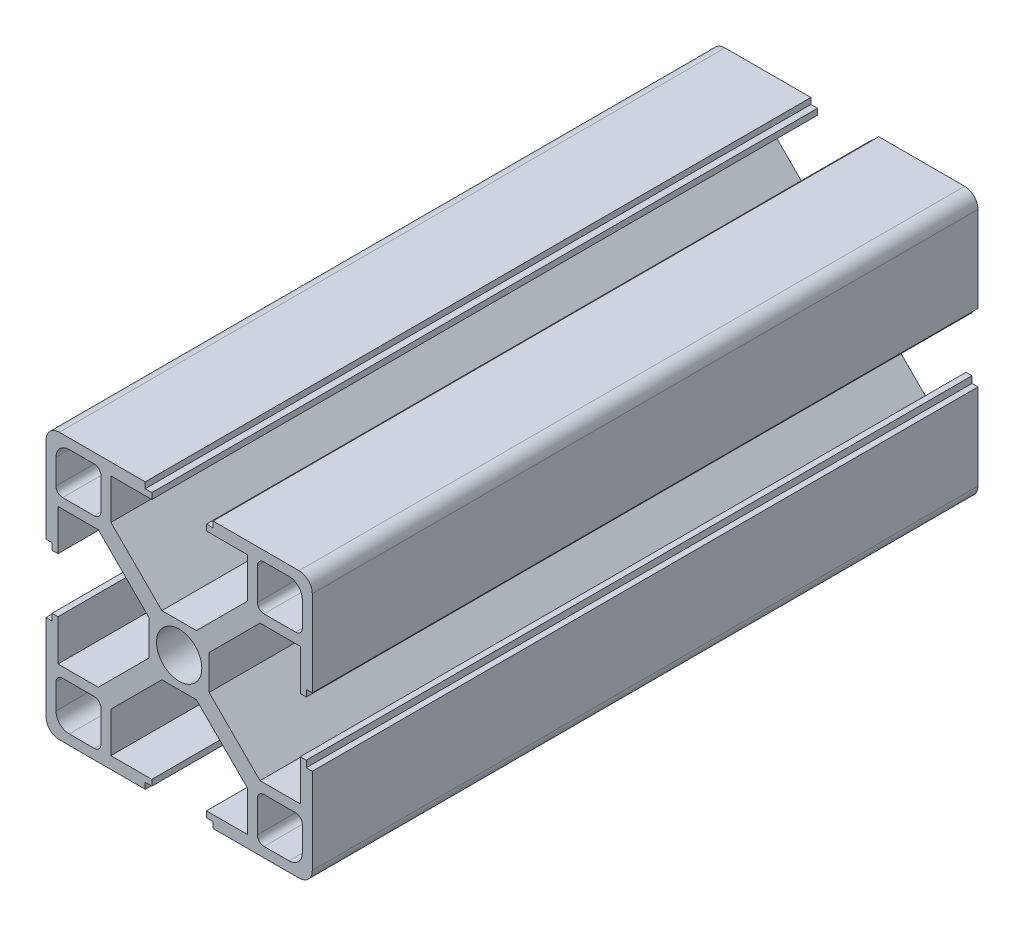
SolidWorks part; units mm, degrees
ref_plane "前视基准面" through (0, 0, 0) normal (0, 0, 1) x (1, 0, 0)
ref_plane "上视基准面" through (0, 0, 0) normal (0, 1, 0) x (1, 0, 0)
ref_plane "右视基准面" through (0, 0, 0) normal (1, 0, 0) x (0, 0, -1)
other "Configuration Table"
sketch "草图1" plane through (0, 0, 0) normal (0, 0, 1) x (1, 0, 0)
  line L5 (-20, 20) -> (20, 20)
  line L6 (-20, 20) -> (-20, -20)
  line L11 (-20, -20) -> (20, -20)
  line L12 (20, 20) -> (20, -20)
  line L25 (-20, 20) -> (20, -20) construction
  line L26 (-20, -20) -> (20, 20) construction
  point P0 (0, 0)
  dimension "D1" = 40
  dimension "D2" = 40
extrude "凸台-拉伸1" add sketch "草图1" along normal blind 100
sketch "草图2" plane through (0, 0, 100) normal (0, 0, 1) x (1, 0, 0)
  line L0 (-20, 0) -> (-18.2, 0)
  line L1 (0, 0) -> (-20, 0)
  line L2 (-21.8, 4.1) -> (-18.2, 4.1)
  line L3 (-21.8, 4.1) -> (-21.8, -4.1)
  line L4 (20, -20) -> (20, 20)
  line L5 (20, 20) -> (-20, 20)
  line L6 (-20, 20) -> (-20, -20)
  line L7 (-20, -20) -> (20, -20)
  line L8 (20, -20) -> (20, 20)
  line L9 (20, 20) -> (-20, 20)
  line L10 (-20, 20) -> (-20, -20)
  line L11 (-20, -20) -> (20, -20)
  line L12 (-21.8, -4.1) -> (-18.2, -4.1)
  line L13 (-18.2, 4.1) -> (-18.2, -4.1)
  line L14 (-21.8, 4.1) -> (-18.2, -4.1) construction
  line L15 (-21.8, -4.1) -> (-18.2, 4.1) construction
  line L16 (-18.2, 10.25) -> (-18.2, -10.25)
  line L17 (-4.5, -2.6) -> (-4.5, 2.6)
  line L18 (-4.5, 4.5) -> (4.5, 4.5)
  line L19 (-4.5, 4.5) -> (-4.5, -4.5)
  line L20 (-4.5, -4.5) -> (4.5, -4.5)
  line L21 (4.5, 4.5) -> (4.5, -4.5)
  line L22 (-4.5, 4.5) -> (4.5, -4.5) construction
  line L23 (-4.5, -4.5) -> (4.5, 4.5) construction
  line L24 (-18.2, 10.25) -> (-12.15, 10.25)
  line L25 (-12.15, 10.25) -> (-4.5, 2.6)
  line L26 (-18.2, -10.25) -> (-12.15, -10.25)
  line L27 (-12.15, -10.25) -> (-4.5, -2.6)
  line L29 (-20.9, -5.1) -> (-19.1, -5.1)
  line L30 (-20.9, -5.1) -> (-20.9, 5.1)
  line L31 (-20.9, 5.1) -> (-19.1, 5.1)
  line L32 (-19.1, -5.1) -> (-19.1, 5.1)
  line L33 (-20.9, -5.1) -> (-19.1, 5.1) construction
  line L34 (-20.9, 5.1) -> (-19.1, -5.1) construction
  circle A0 centre (0, 0) radius 3.4
  point P16 (-18.2, 0)
  point P23 (-4.5, 0)
  line M15 (-20, 20) -> (-20, -20)
  dimension "D4" = 6.8
  dimension "D2" = 1.8
  dimension "D3" = 8.2
  dimension "D5" = 20.5
  dimension "D6" = 9
  dimension "D7" = 9
  dimension "D8" = 5.2
  dimension "D9" = 135
  dimension "D10" = 0.9
  dimension "D11" = 10.2
  dimension "D12" = 135
  dimension "D1" = 0
extrude "切除-拉伸1" cut sketch "草图2" against normal through all contours L26 L19 L17 L1 L13 L16 | L13 L2 L0 M15 | L25 L24 L16 L13 L1 L17 | L13 L0 L12 M15 | A0 | L32 L1 L13 L2 | L32 L12 L13 L1 | L2 L32 L31 L10 | L29 L32 L12 L10 region at (-19.55, 2.05, 100) region at (-19.55, -2.05, 100) region at (-18.65, 2.05, 100) region at (-18.65, -2.05, 100) region at (-19.55, 4.6, 100) region at (-19.55, -4.6, 100) region at (-12.4819, 4.4472, 100) region at (-12.4819, -4.4472, 100) region at (0, 3.3038, 100)
pattern_circular "阵列(圆周)1" count 4 over 360 about axis through (0, 0, 0) along (0, 0, 1) of "切除-拉伸1" reverse direction yes
fillet "圆角1" radius 2 4 edges at (-20, -20, 50) (20, -20, 50) (20, 20, 50) (-20, 20, 50)
sketch "草图3" plane through (0, 0, 100) normal (0, 0, 1) x (1, 0, 0)
  line L60 (-20, -5.1) -> (-20, -18)
  line L61 (-18, -20) -> (-5.1, -20)
  line L62 (-5.1, -20) -> (-5.1, -19.1)
  line L63 (-5.1, -19.1) -> (-4.1, -19.1)
  line L64 (-4.1, -19.1) -> (-4.1, -18.2)
  line L65 (-4.1, -18.2) -> (-10.25, -18.2)
  line L66 (-10.25, -18.2) -> (-10.25, -12.15)
  line L67 (-10.25, -12.15) -> (-2.6, -4.5)
  line L68 (-2.6, -4.5) -> (2.6, -4.5)
  line L69 (2.6, -4.5) -> (10.25, -12.15)
  line L70 (10.25, -12.15) -> (10.25, -18.2)
  line L71 (10.25, -18.2) -> (4.1, -18.2)
  line L72 (4.1, -18.2) -> (4.1, -19.1)
  line L73 (4.1, -19.1) -> (5.1, -19.1)
  line L74 (5.1, -19.1) -> (5.1, -20)
  line L75 (5.1, -20) -> (18, -20)
  line L76 (20, -18) -> (20, -5.1)
  line L77 (20, -5.1) -> (19.1, -5.1)
  line L78 (19.1, -5.1) -> (19.1, -4.1)
  line L79 (19.1, -4.1) -> (18.2, -4.1)
  line L80 (18.2, -4.1) -> (18.2, -10.25)
  line L81 (18.2, -10.25) -> (12.15, -10.25)
  line L82 (12.15, -10.25) -> (4.5, -2.6)
  line L83 (4.5, -2.6) -> (4.5, 2.6)
  line L84 (4.5, 2.6) -> (12.15, 10.25)
  line L85 (12.15, 10.25) -> (18.2, 10.25)
  line L86 (18.2, 10.25) -> (18.2, 4.1)
  line L87 (18.2, 4.1) -> (19.1, 4.1)
  line L88 (19.1, 4.1) -> (19.1, 5.1)
  line L89 (19.1, 5.1) -> (20, 5.1)
  line L90 (20, 5.1) -> (20, 18)
  line L91 (18, 20) -> (5.1, 20)
  line L92 (5.1, 20) -> (5.1, 19.1)
  line L93 (5.1, 19.1) -> (4.1, 19.1)
  line L94 (4.1, 19.1) -> (4.1, 18.2)
  line L95 (4.1, 18.2) -> (10.25, 18.2)
  line L96 (10.25, 18.2) -> (10.25, 12.15)
  line L97 (10.25, 12.15) -> (2.6, 4.5)
  line L98 (2.6, 4.5) -> (-2.6, 4.5)
  line L99 (-2.6, 4.5) -> (-10.25, 12.15)
  line L100 (-10.25, 12.15) -> (-10.25, 18.2)
  line L101 (-10.25, 18.2) -> (-4.1, 18.2)
  line L102 (-4.1, 18.2) -> (-4.1, 19.1)
  line L103 (-4.1, 19.1) -> (-5.1, 19.1)
  line L104 (-5.1, 19.1) -> (-5.1, 20)
  line L105 (-5.1, 20) -> (-18, 20)
  line L106 (-20, 18) -> (-20, 5.1)
  line L107 (-20, 5.1) -> (-19.1, 5.1)
  line L108 (-19.1, 5.1) -> (-19.1, 4.1)
  line L109 (-19.1, 4.1) -> (-18.2, 4.1)
  line L110 (-18.2, 4.1) -> (-18.2, 10.25)
  line L111 (-18.2, 10.25) -> (-12.15, 10.25)
  line L112 (-12.15, 10.25) -> (-4.5, 2.6)
  line L113 (-4.5, 2.6) -> (-4.5, -2.6)
  line L114 (-4.5, -2.6) -> (-12.15, -10.25)
  line L115 (-12.15, -10.25) -> (-18.2, -10.25)
  line L116 (-18.2, -10.25) -> (-18.2, -4.1)
  line L117 (-18.2, -4.1) -> (-19.1, -4.1)
  line L118 (-19.1, -4.1) -> (-19.1, -5.1)
  line L119 (-19.1, -5.1) -> (-20, -5.1)
  line L120 (-20, -5.1) -> (-20, -18)
  line L121 (-18, -20) -> (-5.1, -20)
  line L122 (-5.1, -20) -> (-5.1, -19.1)
  line L123 (-5.1, -19.1) -> (-4.1, -19.1)
  line L124 (-4.1, -19.1) -> (-4.1, -18.2)
  line L125 (-4.1, -18.2) -> (-10.25, -18.2)
  line L126 (-10.25, -18.2) -> (-10.25, -12.15)
  line L127 (-10.25, -12.15) -> (-2.6, -4.5)
  line L128 (-2.6, -4.5) -> (2.6, -4.5)
  line L129 (2.6, -4.5) -> (10.25, -12.15)
  line L130 (10.25, -12.15) -> (10.25, -18.2)
  line L131 (10.25, -18.2) -> (4.1, -18.2)
  line L132 (4.1, -18.2) -> (4.1, -19.1)
  line L133 (4.1, -19.1) -> (5.1, -19.1)
  line L134 (5.1, -19.1) -> (5.1, -20)
  line L135 (5.1, -20) -> (18, -20)
  line L136 (20, -18) -> (20, -5.1)
  line L137 (20, -5.1) -> (19.1, -5.1)
  line L138 (19.1, -5.1) -> (19.1, -4.1)
  line L139 (19.1, -4.1) -> (18.2, -4.1)
  line L140 (18.2, -4.1) -> (18.2, -10.25)
  line L141 (18.2, -10.25) -> (12.15, -10.25)
  line L142 (12.15, -10.25) -> (4.5, -2.6)
  line L143 (4.5, -2.6) -> (4.5, 2.6)
  line L144 (4.5, 2.6) -> (12.15, 10.25)
  line L145 (12.15, 10.25) -> (18.2, 10.25)
  line L146 (18.2, 10.25) -> (18.2, 4.1)
  line L147 (18.2, 4.1) -> (19.1, 4.1)
  line L148 (19.1, 4.1) -> (19.1, 5.1)
  line L149 (19.1, 5.1) -> (20, 5.1)
  line L150 (20, 5.1) -> (20, 18)
  line L151 (18, 20) -> (5.1, 20)
  line L152 (5.1, 20) -> (5.1, 19.1)
  line L153 (5.1, 19.1) -> (4.1, 19.1)
  line L154 (4.1, 19.1) -> (4.1, 18.2)
  line L155 (4.1, 18.2) -> (10.25, 18.2)
  line L156 (10.25, 18.2) -> (10.25, 12.15)
  line L157 (10.25, 12.15) -> (2.6, 4.5)
  line L158 (2.6, 4.5) -> (-2.6, 4.5)
  line L159 (-2.6, 4.5) -> (-10.25, 12.15)
  line L160 (-10.25, 12.15) -> (-10.25, 18.2)
  line L161 (-10.25, 18.2) -> (-4.1, 18.2)
  line L162 (-4.1, 18.2) -> (-4.1, 19.1)
  line L163 (-4.1, 19.1) -> (-5.1, 19.1)
  line L164 (-5.1, 19.1) -> (-5.1, 20)
  line L165 (-5.1, 20) -> (-18, 20)
  line L166 (-20, 18) -> (-20, 5.1)
  line L167 (-20, 5.1) -> (-19.1, 5.1)
  line L168 (-19.1, 5.1) -> (-19.1, 4.1)
  line L169 (-19.1, 4.1) -> (-18.2, 4.1)
  line L170 (-18.2, 4.1) -> (-18.2, 10.25)
  line L171 (-18.2, 10.25) -> (-12.15, 10.25)
  line L172 (-12.15, 10.25) -> (-4.5, 2.6)
  line L173 (-4.5, 2.6) -> (-4.5, -2.6)
  line L174 (-4.5, -2.6) -> (-12.15, -10.25)
  line L175 (-12.15, -10.25) -> (-18.2, -10.25)
  line L176 (-18.2, -10.25) -> (-18.2, -4.1)
  line L177 (-18.2, -4.1) -> (-19.1, -4.1)
  line L178 (-19.1, -4.1) -> (-19.1, -5.1)
  line L179 (-19.1, -5.1) -> (-20, -5.1)
  arc A4 (-20, -18) -> (-18, -20) centre (-18, -18) ccw
  arc A5 (18, -20) -> (20, -18) centre (18, -18) ccw
  arc A6 (20, 18) -> (18, 20) centre (18, 18) ccw
  arc A7 (-18, 20) -> (-20, 18) centre (-18, 18) ccw
  arc A8 (-20, -18) -> (-18, -20) centre (-18, -18) ccw
  arc A9 (18, -20) -> (20, -18) centre (18, -18) ccw
  arc A10 (20, 18) -> (18, 20) centre (18, 18) ccw
  arc A11 (-18, 20) -> (-20, 18) centre (-18, 18) ccw
  dimension "D1" = 0
sketch "草图4" plane through (0, 0, 100) normal (0, 0, 1) x (1, 0, 0)
  line L0 (-20, 18) -> (-18, 20)
  line L4 (-5.1, 20) -> (-18, 20) construction
  line L9 (-18, 20) -> (-20, 20)
  line L14 (-20, 20) -> (-20, 18)
  line L15 (-10.25, 12.15) -> (-12.15, 10.25)
  line L16 (-12.15, 10.25) -> (-10.25, 10.25)
  line L17 (-10.25, 10.25) -> (-10.25, 12.15)
  line L18 (-20, 20) -> (-10.25, 10.25)
  line L19 (-20, 20) -> (-10.25, 20)
  line L20 (-20, 20) -> (-20, 10.25)
  line L21 (-20, 10.25) -> (-10.25, 10.25)
  line L22 (-10.25, 20) -> (-10.25, 10.25)
  line L24 (-11.75, 11.75) -> (-18.5, 11.75)
  line L25 (-11.75, 11.75) -> (-11.75, 18.5)
  line L26 (-11.75, 18.5) -> (-18.5, 18.5)
  line L27 (-18.5, 11.75) -> (-18.5, 18.5)
  line L28 (-11.75, 11.75) -> (-18.5, 18.5) construction
  line L29 (-11.75, 18.5) -> (-18.5, 11.75) construction
  arc A0 (-18, 20) -> (-20, 18) centre (-18, 18) ccw construction
  point P14 (-15.125, 15.125)
  dimension "D1" = 1.5
extrude "切除-拉伸2" cut sketch "草图4" against normal through all both and the other way through all contours L27 L24 L18 | L25 L26 L18 region at (-14, 16.25, 100) region at (-16.25, 14, 100)
fillet "圆角2" radius 1 3 edges at (-11.75, 18.5, 50) (-11.75, 11.75, 50) (-18.5, 11.75, 50)
fillet "圆角4" radius 2 1 edges at (-18.5, 18.5, 50)
pattern_circular "阵列(圆周)2" count 4 over 360 about axis through (0, 0, 0) along (0, 0, 1) of "切除-拉伸2", "圆角2", "圆角4" reverse direction yes
